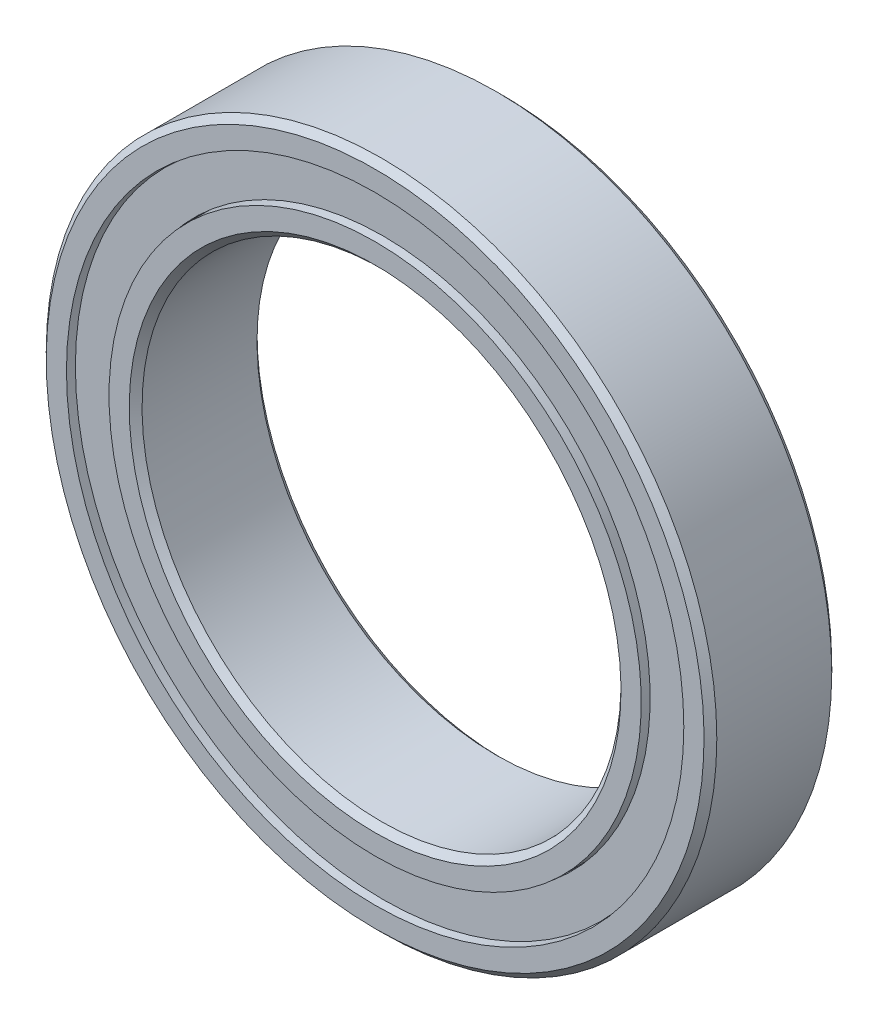
SolidWorks part; units mm, degrees
ref_plane "Front Plane" through (0, 0, 0) normal (0, 0, 1) x (1, 0, 0)
ref_plane "Top Plane" through (0, 0, 0) normal (0, 1, 0) x (1, 0, 0)
ref_plane "Right Plane" through (0, 0, 0) normal (1, 0, 0) x (0, 0, -1)
sketch "Sketch1" plane through (0, 0, 0) normal (0, 0, 1) x (1, 0, 0)
  circle A0 centre (0, 0) radius 10.5
  circle A1 centre (0, 0) radius 7.5
  dimension "OD" = 21
  dimension "ID" = 15
sketch "Sketch8" plane through (0, 0, 0) normal (1, 0, 0) x (0, 0, -1)
  line L1 (-2, 10.5) -> (2, 10.5)
  line L2 (-2, 10.5) -> (-2, -10.5)
  line L3 (-2, -10.5) -> (2, -10.5)
  line L4 (2, 10.5) -> (2, -10.5)
  line L5 (-2, 10.5) -> (2, -10.5) construction
  line L6 (-2, -10.5) -> (2, 10.5) construction
  point P0 (0, 0)
  point P6 (0, -10.5)
  dimension "Width" = 4
sketch "Sketch5" plane through (0, 0, 0) normal (1, 0, 0) x (0, 0, -1)
  line L0 (-2, 0) -> (2, 0) construction
  line L1 (0, 10.5) -> (0, -10.5) construction
  line L2 (1.8, 10.5) -> (-1.8, 10.5)
  line L3 (-1.8, 10.5) -> (-2, 10.3)
  line L4 (-2, 10.3) -> (-2, 9.6667)
  line L5 (-2, 9.6667) -> (-0.8889, 9.6667)
  line L6 (2, 9.6667) -> (0.8889, 9.6667)
  line L7 (2, 10.3) -> (2, 9.6667)
  line L8 (1.8, 10.5) -> (2, 10.3)
  line L9 (0, 10.5) -> (0, 9) construction
  line L10 (0, 9) -> (0, 7.5) construction
  line L11 (-1.1111, 9) -> (-2, 9) construction
  line L12 (1.3651, 8.3587) -> (1.7461, 8.3587)
  line L13 (-1.3651, 8.3587) -> (-1.7461, 8.3587)
  line L14 (-1.3651, 8.3587) -> (-1.3651, 9.6413)
  line L15 (-1.3651, 9.6413) -> (-1.7461, 9.6413)
  line L16 (-1.7461, 8.3587) -> (-1.7461, 9.6413)
  line L17 (-1.3651, 8.3587) -> (-1.7461, 9.6413) construction
  line L18 (-1.3651, 9.6413) -> (-1.7461, 8.3587) construction
  line L19 (1.7461, 8.3587) -> (1.7461, 9.6413)
  line L20 (1.3651, 9.6413) -> (1.7461, 9.6413)
  line L21 (1.3651, 8.3587) -> (1.3651, 9.6413)
  line L22 (0, 10.5) -> (0, -10.5) construction
  line L23 (2, 0) -> (2, 10.5) construction
  line L24 (2, 10.5) -> (1.8, 10.5) construction
  line L25 (-2, 0) -> (-2, 10.5) construction
  line L26 (-2, 10.5) -> (-1.8, 10.5) construction
  line L27 (2, 0) -> (2, -10.5) construction
  line L28 (-2, 0) -> (-2, -10.5) construction
  line L29 (-2, -10.5) -> (2, -10.5) construction
  arc A0 (-0.8889, 9.6667) -> (0.8889, 9.6667) centre (0, 9) cw
  circle A1 centre (0, 9) radius 1.1111 construction
  point P14 (0, 7.5)
  point P15 (-1.5556, 9)
  dimension "D1" = 45
  dimension "D2" = 0.2
  dimension "D3" = 1.7778
  dimension "D4" = 0.6667
  dimension "D5" = 0.381
  dimension "D6" = 0.0254
revolve "Revolve1" add sketch "Sketch5" angle 360 about L0
sketch "Sketch3" plane through (0, 0, 0) normal (1, 0, 0) x (0, 0, -1)
  line L0 (-2, 8.3333) -> (-0.8889, 8.3333)
  line L1 (0, 10.5) -> (0, -10.5) construction
  line L2 (-2, 10.3) -> (-2, 9.6667) construction
  line L3 (-2, 8.3333) -> (-2, 7.7)
  line L4 (-1.8, 10.5) -> (-2, 10.3) construction
  line L5 (-2, 7.7) -> (-1.8, 7.5)
  line L6 (-1.8, 7.5) -> (1.8, 7.5)
  line L7 (1.8, 10.5) -> (1.8, -10.5) construction
  line L8 (1.8, 7.5) -> (2, 7.7)
  line L9 (2, -10.3) -> (2, 10.3) construction
  line L10 (2, 7.7) -> (2, 8.3333)
  line L11 (2, 8.3333) -> (0.8889, 8.3333)
  line L13 (1.8, 10.5) -> (2, 10.3) construction
  arc A0 (0.8889, 9.6667) -> (-0.8889, 9.6667) centre (0, 9) ccw construction
  arc A1 (0.8889, 8.3333) -> (-0.8889, 8.3333) centre (0, 9) cw
revolve "Revolve3" add sketch "Sketch3" angle 360 about L0
sketch "Sketch4" plane through (0, 0, 0) normal (1, 0, 0) x (0, 0, -1)
  line L0 (-1.1111, 9) -> (1.1111, 9)
  arc A2 (-1.1111, 9) -> (1.1111, 9) centre (0, 9) cw
  arc A3 (0.8889, 9.6667) -> (-0.8889, 9.6667) centre (0, 9) ccw construction
revolve "Revolve4" add sketch "Sketch4" angle 360 about L0
pattern_circular "CirPattern1" count 14 every 25.714 of bodies 104
ref_axis "Center Axis 1" through (0, 0, -1.8) along (0, 0, 1)
equation "\"D2@Sketch5\" = \"Width@Sketch8\" * .05"
equation "\"D3@Sketch5\" = \"Width@Sketch8\" / 2.25"
equation "\"D4@Sketch5\"=((\"OD@Sketch1\"-\"ID@Sketch1\")/2)/4.5"
equation "\"D2@CirPattern1\" = 360/\"Balls@CirPattern1\""
